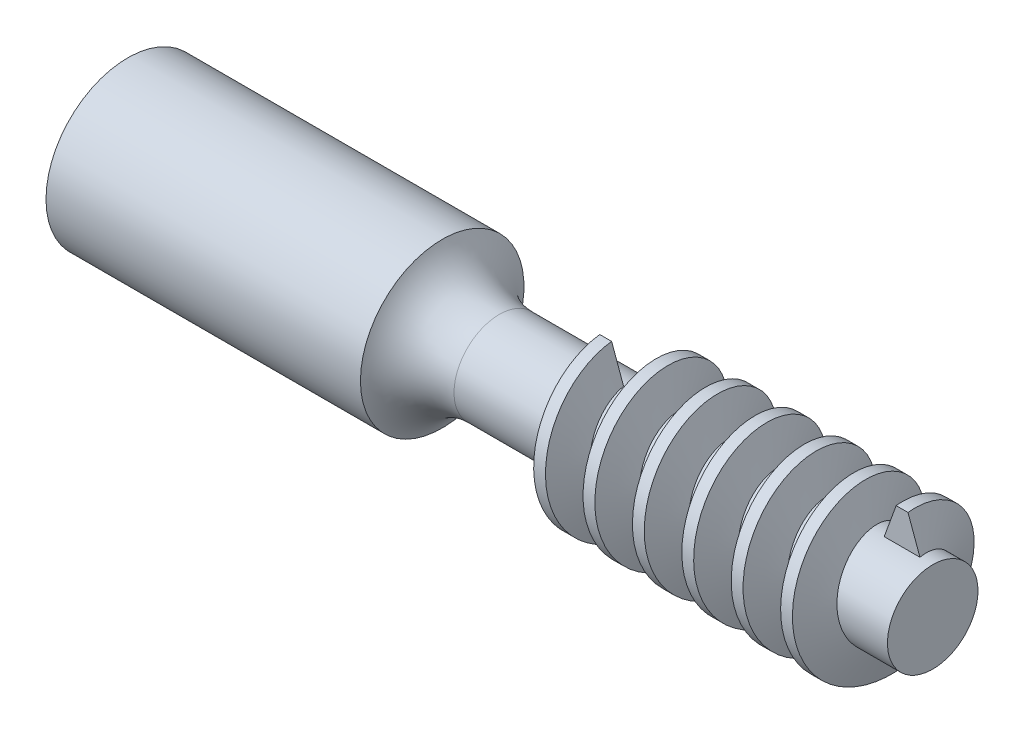
SolidWorks part; units mm, degrees
ref_plane "Front Plane" through (0, 0, 0) normal (0, 0, 1) x (1, 0, 0)
ref_plane "Top Plane" through (0, 0, 0) normal (0, 1, 0) x (1, 0, 0)
ref_plane "Right Plane" through (0, 0, 0) normal (1, 0, 0) x (0, 0, -1)
sketch "Sketch1" plane through (0, 0, 0) normal (0, 0, 1) x (1, 0, 0)
  line L0 (-1.42, 0) -> (1.42, 0) construction
  line L1 (-1.42, 0) -> (-0.47, 2.61)
  line L2 (-0.47, 2.61) -> (0.47, 2.61)
  line L3 (0.47, 2.61) -> (1.42, 0)
  line L4 (-1.42, 0) -> (-2.4, 0) construction
  line L5 (-0.47, 2.61) -> (-3.3499, 2.61) construction
  line L6 (-3.3499, 2.61) -> (-2.4, 0) construction
  line L7 (-1.42, 0) -> (1.42, 0)
  point P8 (0, 0)
  point P10 (0, 2.61)
  dimension "D1" = 70
  dimension "D2" = 70
  dimension "D3" = 0.94
  dimension "D4" = 0.98
  dimension "D5" = 2.61
sketch "Sketch2" plane through (0, 0, 0) normal (1, 0, 0) x (0, 0, -1)
  circle A0 centre (0, -3.599) radius 3.599
  dimension "D1" = 7.198
curve "Helix/Spiral1" pitch 3.927 height 23.5619 radius 3.599 centre (0, -3.599, 0) axis (1, 0, 0) start towards (0, 1, 0)
sweep "Sweep1" add profiles "Sketch1" path "Helix/Spiral1"
extrude "Boss-Extrude1" add sketch "Sketch2<2>" along normal blind 26 and the other way blind 13
sketch "Sketch2<2>" plane through (0, 0, 0) normal (1, 0, 0) x (0, 0, -1) same geometry as "Sketch2"
ref_axis "Axis1" through (26, -3.599, 0) along (-1, 0, 0)
sketch "Sketch3" plane through (-13, 0, 0) normal (-1, 0, 0) x (0, 0, 1)
  circle A2 centre (0, -3.599) radius 6.5
  dimension "D1" = 13
extrude "Boss-Extrude2" add sketch "Sketch3" along normal blind 25
sketch "Sketch4" plane through (-38, 0, 0) normal (-1, 0, 0) x (0, 0, 1)
  line L2 (2, -5.099) -> (2, -2.099)
  circle A0 centre (0, -3.599) radius 2.5
  dimension "D1" = 5
  dimension "D2" = 3
extrude "Cut-Extrude1" cut sketch "Sketch4" against normal blind 13 contours L2 A0 region at (-38, -3.599, -0.1209)
fillet "Fillet1" radius 5 1 edges at (-13, -3.599, -3.599)
